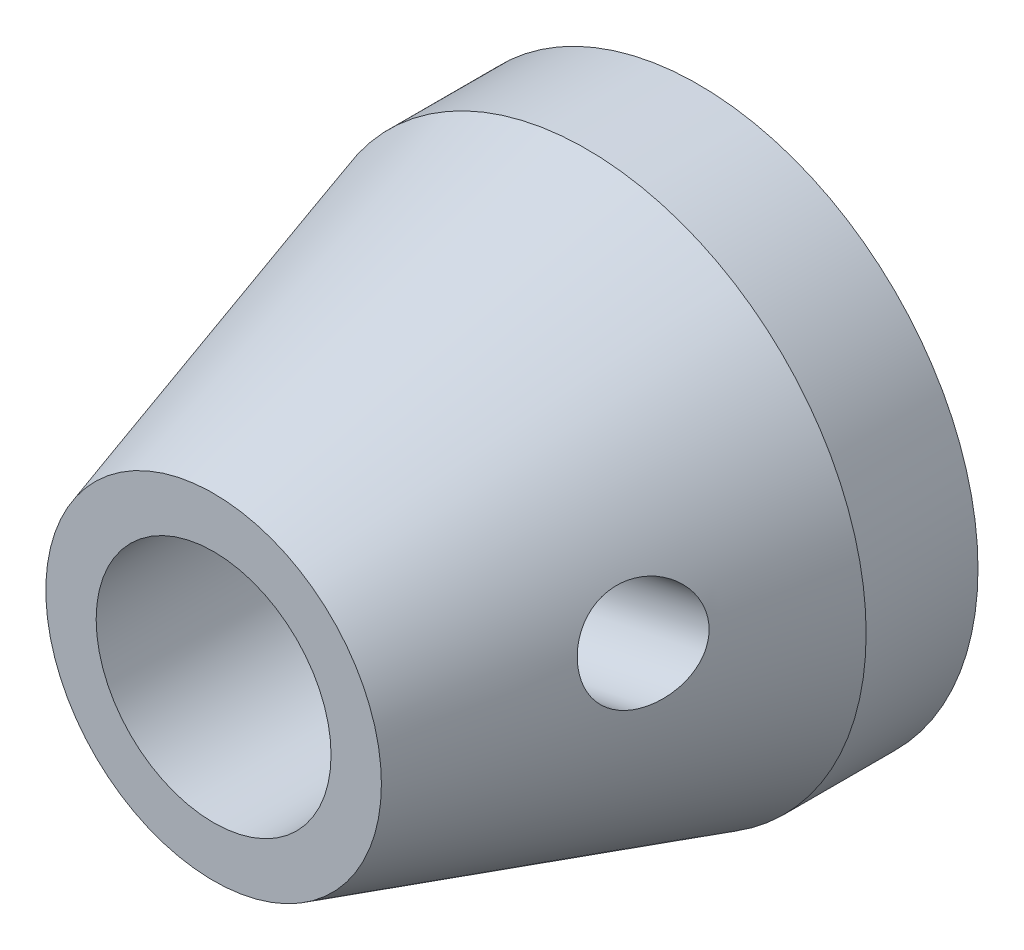
SolidWorks part; units mm, degrees
ref_plane "前视基准面" through (0, 0, 0) normal (0, 0, 1) x (1, 0, 0)
ref_plane "上视基准面" through (0, 0, 0) normal (0, 1, 0) x (1, 0, 0)
ref_plane "右视基准面" through (0, 0, 0) normal (1, 0, 0) x (0, 0, -1)
other "Configuration Table"
sketch "草图6" plane through (0, 0, 0) normal (0, 0, 1) x (1, 0, 0)
  circle A0 centre (18.1431, 29.9368) radius 7.5
  dimension "D1" = 15
extrude "凸台-拉伸1" add sketch "草图6" along normal blind 3
sketch "草图7" plane through (0, 0, 3) normal (0, 0, 1) x (1, 0, 0)
  circle A0 centre (18.1431, 29.9368) radius 4.5
  circle A1 centre (18.1431, 29.9368) radius 3.15
  dimension "D1" = 9
  dimension "D2" = 6.3
extrude "凸台-拉伸2" add sketch "草图7" along normal blind 10
sketch "草图9" plane through (0, 0, 3) normal (0, 0, 1) x (1, 0, 0)
  circle A1 centre (18.1431, 29.9368) radius 1.65
  dimension "D1" = 3.3
extrude "切除-拉伸1" cut sketch "草图9" against normal up to surface (3 mm away) up to face at (25.6431, 29.9368, 0)
ref_plane "基准面1" through (18.9215, 3.9057, 0) normal (-0.9794, -0.2022, 0) x (0, 0, 1)
chamfer "倒角1" distance 3 distance2 10 1 edges at (22.6431, 29.9368, 3) first distance on face at (22.6431, 29.9368, 3)
sketch "草图10" plane through (18.9215, 3.9057, 0) normal (-0.9794, -0.2022, 0) x (0, 0, 1)
  line L0 (0, 25.6511) -> (13, 25.6511) construction
  line L1 (0, 33.1511) -> (0, 18.1511) construction
  line L2 (13, 21.1511) -> (13, 30.1511) construction
  circle A0 centre (7.5, 25.6511) radius 1.35
  dimension "D1" = 2.7
  dimension "D2" = 5.5
extrude "切除-拉伸2" cut sketch "草图10" against normal through all both and the other way through all
